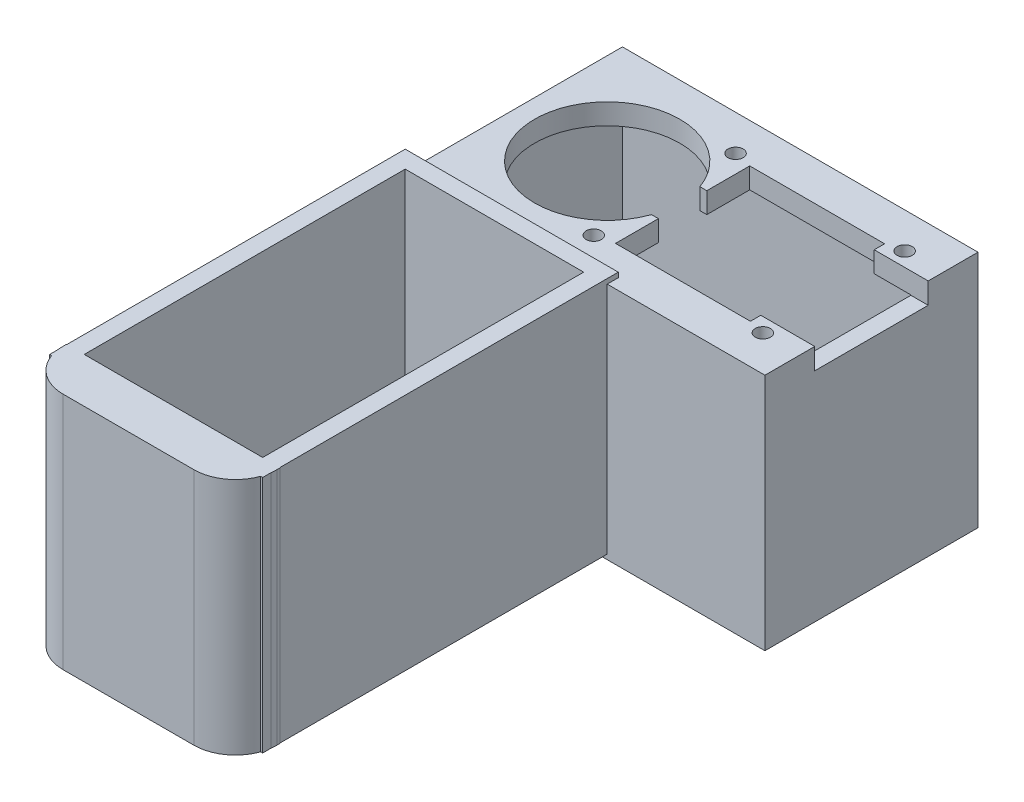
SolidWorks part; units mm, degrees
ref_plane "Front Plane" through (0, 0, 0) normal (0, 0, 1) x (1, 0, 0)
ref_plane "Top Plane" through (0, 0, 0) normal (0, 1, 0) x (1, 0, 0)
ref_plane "Right Plane" through (0, 0, 0) normal (1, 0, 0) x (0, 0, -1)
ref_plane "PZ_m38_200" through (0, 0, -38.2) normal (0, 0, 1) x (1, 0, 0)
sketch "S_box1" plane through (0, 0, -38.2) normal (0, 0, 1) x (1, 0, 0)
  line L0 (-15.4, -37.4) -> (15.4, -37.4)
  line L1 (15.4, -37.4) -> (15.4, -2.9)
  line L2 (15.4, -2.9) -> (-15.4, -2.9)
  line L3 (-15.4, -2.9) -> (-15.4, -37.4)
  dimension "P1" = 15.4
  dimension "P2" = 37.4
  dimension "P3" = 15.4
  dimension "P4" = 37.4
  dimension "P5" = 15.4
  dimension "P6" = 2.9
  dimension "P7" = 15.4
  dimension "P8" = 2.9
extrude "Boss_1" add sketch "S_box1" along normal blind 2.5
ref_plane "PZ_p10_700" through (0, 0, 10.7) normal (0, 0, 1) x (1, 0, 0)
sketch "S_box2" plane through (0, 0, 10.7) normal (0, 0, 1) x (1, 0, 0)
  line L0 (-15.4, -37.4) -> (15.4, -37.4)
  line L1 (15.4, -37.4) -> (15.4, -2.9)
  line L2 (15.4, -2.9) -> (-15.4, -2.9)
  line L3 (-15.4, -2.9) -> (-15.4, -37.4)
  dimension "P1" = 15.4
  dimension "P2" = 37.4
  dimension "P3" = 15.4
  dimension "P4" = 37.4
  dimension "P5" = 15.4
  dimension "P6" = 2.9
  dimension "P7" = 15.4
  dimension "P8" = 2.9
extrude "Boss_2" add sketch "S_box2" along normal blind 2.5
sketch "S_box3" plane through (0, 0, -38.2) normal (0, 0, 1) x (1, 0, 0)
  line L0 (-15.4, -37.4) -> (-12.9, -37.4)
  line L1 (-12.9, -37.4) -> (-12.9, -2.9)
  line L2 (-12.9, -2.9) -> (-15.4, -2.9)
  line L3 (-15.4, -2.9) -> (-15.4, -37.4)
  dimension "P1" = 15.4
  dimension "P2" = 37.4
  dimension "P3" = 12.9
  dimension "P4" = 37.4
  dimension "P5" = 12.9
  dimension "P6" = 2.9
  dimension "P7" = 15.4
  dimension "P8" = 2.9
extrude "Boss_3" add sketch "S_box3" along normal blind 51.4
sketch "S_box4" plane through (0, 0, -38.2) normal (0, 0, 1) x (1, 0, 0)
  line L0 (12.9, -37.4) -> (15.4, -37.4)
  line L1 (15.4, -37.4) -> (15.4, -2.9)
  line L2 (15.4, -2.9) -> (12.9, -2.9)
  line L3 (12.9, -2.9) -> (12.9, -37.4)
  dimension "P1" = 12.9
  dimension "P2" = 37.4
  dimension "P3" = 15.4
  dimension "P4" = 37.4
  dimension "P5" = 15.4
  dimension "P6" = 2.9
  dimension "P7" = 12.9
  dimension "P8" = 2.9
extrude "Boss_4" add sketch "S_box4" along normal blind 51.4
sketch "S_box5" plane through (0, 0, -38.2) normal (0, 0, 1) x (1, 0, 0)
  line L0 (-15.4, -37.4) -> (15.4, -37.4)
  line L1 (15.4, -37.4) -> (15.4, -34.4)
  line L2 (15.4, -34.4) -> (-15.4, -34.4)
  line L3 (-15.4, -34.4) -> (-15.4, -37.4)
  dimension "P1" = 15.4
  dimension "P2" = 37.4
  dimension "P3" = 15.4
  dimension "P4" = 37.4
  dimension "P5" = 15.4
  dimension "P6" = 34.4
  dimension "P7" = 15.4
  dimension "P8" = 34.4
extrude "Boss_5" add sketch "S_box5" along normal blind 51.4
ref_plane "PZ_m67_400" through (0, 0, -67.4) normal (0, 0, 1) x (1, 0, 0)
sketch "S_box6" plane through (0, 0, -67.4) normal (0, 0, 1) x (1, 0, 0)
  line L0 (-13.2, -38.1) -> (-10.7, -38.1)
  line L1 (-10.7, -38.1) -> (-10.7, -3.6)
  line L2 (-10.7, -3.6) -> (-13.2, -3.6)
  line L3 (-13.2, -3.6) -> (-13.2, -38.1)
  dimension "P1" = 13.2
  dimension "P2" = 38.1
  dimension "P3" = 10.7
  dimension "P4" = 38.1
  dimension "P5" = 10.7
  dimension "P6" = 3.6
  dimension "P7" = 13.2
  dimension "P8" = 3.6
extrude "Boss_6" add sketch "S_box6" along normal blind 30.8
sketch "S_box7" plane through (0, 0, -67.4) normal (0, 0, 1) x (1, 0, 0)
  line L0 (35.7, -38.1) -> (38.2, -38.1)
  line L1 (38.2, -38.1) -> (38.2, -3.6)
  line L2 (38.2, -3.6) -> (35.7, -3.6)
  line L3 (35.7, -3.6) -> (35.7, -38.1)
  dimension "P1" = 35.7
  dimension "P2" = 38.1
  dimension "P3" = 38.2
  dimension "P4" = 38.1
  dimension "P5" = 38.2
  dimension "P6" = 3.6
  dimension "P7" = 35.7
  dimension "P8" = 3.6
extrude "Boss_7" add sketch "S_box7" along normal blind 30.8
sketch "S_box8" plane through (0, 0, -67.4) normal (0, 0, 1) x (1, 0, 0)
  line L0 (-13.2, -38.1) -> (38.2, -38.1)
  line L1 (38.2, -38.1) -> (38.2, -3.6)
  line L2 (38.2, -3.6) -> (-13.2, -3.6)
  line L3 (-13.2, -3.6) -> (-13.2, -38.1)
  dimension "P1" = 13.2
  dimension "P2" = 38.1
  dimension "P3" = 38.2
  dimension "P4" = 38.1
  dimension "P5" = 38.2
  dimension "P6" = 3.6
  dimension "P7" = 13.2
  dimension "P8" = 3.6
extrude "Boss_8" add sketch "S_box8" along normal blind 2.5
ref_plane "PZ_m39_100" through (0, 0, -39.1) normal (0, 0, 1) x (1, 0, 0)
sketch "S_box9" plane through (0, 0, -39.1) normal (0, 0, 1) x (1, 0, 0)
  line L0 (-13.2, -38.1) -> (38.2, -38.1)
  line L1 (38.2, -38.1) -> (38.2, -3.6)
  line L2 (38.2, -3.6) -> (-13.2, -3.6)
  line L3 (-13.2, -3.6) -> (-13.2, -38.1)
  dimension "P1" = 13.2
  dimension "P2" = 38.1
  dimension "P3" = 38.2
  dimension "P4" = 38.1
  dimension "P5" = 38.2
  dimension "P6" = 3.6
  dimension "P7" = 13.2
  dimension "P8" = 3.6
extrude "Boss_9" add sketch "S_box9" along normal blind 2.5
sketch "S_box10" plane through (0, 0, -67.4) normal (0, 0, 1) x (1, 0, 0)
  line L0 (-13.2, -6.6) -> (38.2, -6.6)
  line L1 (38.2, -6.6) -> (38.2, -3.6)
  line L2 (38.2, -3.6) -> (-13.2, -3.6)
  line L3 (-13.2, -3.6) -> (-13.2, -6.6)
  dimension "P1" = 13.2
  dimension "P2" = 6.6
  dimension "P3" = 38.2
  dimension "P4" = 6.6
  dimension "P5" = 38.2
  dimension "P6" = 3.6
  dimension "P7" = 13.2
  dimension "P8" = 3.6
extrude "Boss_10" add sketch "S_box10" along normal blind 30.8
ref_plane "PY_m37_400" through (0, -37.4, 0) normal (0, 1, 0) x (1, 0, 0)
sketch "S_prism11" plane through (0, -37.4, 0) normal (0, 1, 0) x (1, 0, 0)
  line L0 (-15.45, -10.75) -> (15.45, -10.75)
  line L1 (15.45, -10.75) -> (15.45, -11.2)
  line L2 (9.45, -17.2) -> (-9.45, -17.2)
  line L3 (-15.45, -11.2) -> (-15.45, -10.75)
  arc A0 (15.45, -11.2) -> (9.45, -17.2) centre (9.4499, -11.1999) cw
  arc A1 (-9.45, -17.2) -> (-15.45, -11.2) centre (-9.4499, -11.1999) cw
extrude "Boss_11" add sketch "S_prism11" along normal blind 34.5
ref_plane "PY_m37_500" through (0, -37.5, 0) normal (0, 1, 0) x (1, 0, 0)
sketch "S_hole12" plane through (0, -37.5, 0) normal (0, 1, 0) x (1, 0, 0)
  circle A0 centre (0, 0) radius 10.5
  dimension "D1_S_hole12" = 21
extrude "Hole_12" cut sketch "S_hole12" along normal blind 3.2
ref_plane "PZ_m30_400" through (0, 0, -30.4) normal (0, 0, 1) x (1, 0, 0)
sketch "S_cut13" plane through (0, 0, -30.4) normal (0, 0, 1) x (1, 0, 0)
  line L0 (-9.7, -37.5) -> (9.7, -37.5)
  line L1 (9.7, -37.5) -> (9.7, -34.35)
  line L2 (9.7, -34.35) -> (-9.7, -34.35)
  line L3 (-9.7, -34.35) -> (-9.7, -37.5)
  dimension "P1" = 9.7
  dimension "P2" = 37.5
  dimension "P3" = 9.7
  dimension "P4" = 37.5
  dimension "P5" = 9.7
  dimension "P6" = 34.35
  dimension "P7" = 9.7
  dimension "P8" = 34.35
extrude "Pocket_13" cut sketch "S_cut13" along normal blind 19.5
ref_plane "PZ_m38_700" through (0, 0, -38.7) normal (0, 0, 1) x (1, 0, 0)
sketch "S_cut14" plane through (0, 0, -38.7) normal (0, 0, 1) x (1, 0, 0)
  line L0 (-8.2, -37.5) -> (8.2, -37.5)
  line L1 (8.2, -37.5) -> (8.2, -34.35)
  line L2 (8.2, -34.35) -> (-8.2, -34.35)
  line L3 (-8.2, -34.35) -> (-8.2, -37.5)
  dimension "P1" = 8.2
  dimension "P2" = 37.5
  dimension "P3" = 8.2
  dimension "P4" = 37.5
  dimension "P5" = 8.2
  dimension "P6" = 34.35
  dimension "P7" = 8.2
  dimension "P8" = 34.35
extrude "Pocket_14" cut sketch "S_cut14" along normal blind 8.3
ref_plane "PZ_m11_000" through (0, 0, -11) normal (0, 0, 1) x (1, 0, 0)
sketch "S_cut15" plane through (0, 0, -11) normal (0, 0, 1) x (1, 0, 0)
  line L0 (-3.5, -37.5) -> (3.5, -37.5)
  line L1 (3.5, -37.5) -> (3.5, -34.35)
  line L2 (3.5, -34.35) -> (-3.5, -34.35)
  line L3 (-3.5, -34.35) -> (-3.5, -37.5)
  dimension "P1" = 3.5
  dimension "P2" = 37.5
  dimension "P3" = 3.5
  dimension "P4" = 37.5
  dimension "P5" = 3.5
  dimension "P6" = 34.35
  dimension "P7" = 3.5
  dimension "P8" = 34.35
extrude "Pocket_15" cut sketch "S_cut15" along normal blind 11
sketch "S_hole16" plane through (0, -37.5, 0) normal (0, 1, 0) x (1, 0, 0)
  circle A0 centre (-10.25, 8.3) radius 1.1
  dimension "D1_S_hole16" = 2.2
  dimension "P2" = 10.25
  dimension "P3" = 8.3
extrude "Hole_16" cut sketch "S_hole16" along normal blind 3.2
sketch "S_hole17" plane through (0, -37.5, 0) normal (0, 1, 0) x (1, 0, 0)
  circle A0 centre (10.25, 8.3) radius 1.1
  dimension "D1_S_hole17" = 2.2
  dimension "P2" = 10.25
  dimension "P3" = 8.3
extrude "Hole_17" cut sketch "S_hole17" along normal blind 3.2
sketch "S_hole18" plane through (0, -37.5, 0) normal (0, 1, 0) x (1, 0, 0)
  circle A0 centre (-10.25, 32.75) radius 1.1
  dimension "D1_S_hole18" = 2.2
  dimension "P2" = 10.25
  dimension "P3" = 32.75
extrude "Hole_18" cut sketch "S_hole18" along normal blind 3.2
sketch "S_hole19" plane through (0, -37.5, 0) normal (0, 1, 0) x (1, 0, 0)
  circle A0 centre (10.25, 32.75) radius 1.1
  dimension "D1_S_hole19" = 2.2
  dimension "P2" = 10.25
  dimension "P3" = 32.75
extrude "Hole_19" cut sketch "S_hole19" along normal blind 3.2
ref_plane "PY_m6_700" through (0, -6.7, 0) normal (0, 1, 0) x (1, 0, 0)
sketch "S_hole20" plane through (0, -6.7, 0) normal (0, 1, 0) x (1, 0, 0)
  circle A0 centre (0, 52) radius 10.5
  dimension "D1_S_hole20" = 21
  dimension "P2" = 52
extrude "Hole_20" cut sketch "S_hole20" along normal blind 3.2
ref_plane "PZ_m61_700" through (0, 0, -61.7) normal (0, 0, 1) x (1, 0, 0)
sketch "S_cut21" plane through (0, 0, -61.7) normal (0, 0, 1) x (1, 0, 0)
  line L0 (10.9, -6.65) -> (30.4, -6.65)
  line L1 (30.4, -6.65) -> (30.4, -3.5)
  line L2 (30.4, -3.5) -> (10.9, -3.5)
  line L3 (10.9, -3.5) -> (10.9, -6.65)
  dimension "P1" = 10.9
  dimension "P2" = 6.65
  dimension "P3" = 30.4
  dimension "P4" = 6.65
  dimension "P5" = 30.4
  dimension "P6" = 3.5
  dimension "P7" = 10.9
  dimension "P8" = 3.5
extrude "Pocket_21" cut sketch "S_cut21" along normal blind 19.4
ref_plane "PZ_m60_200" through (0, 0, -60.2) normal (0, 0, 1) x (1, 0, 0)
sketch "S_cut22" plane through (0, 0, -60.2) normal (0, 0, 1) x (1, 0, 0)
  line L0 (30.4, -6.65) -> (38.7, -6.65)
  line L1 (38.7, -6.65) -> (38.7, -3.5)
  line L2 (38.7, -3.5) -> (30.4, -3.5)
  line L3 (30.4, -3.5) -> (30.4, -6.65)
  dimension "P1" = 30.4
  dimension "P2" = 6.65
  dimension "P3" = 38.7
  dimension "P4" = 6.65
  dimension "P5" = 38.7
  dimension "P6" = 3.5
  dimension "P7" = 30.4
  dimension "P8" = 3.5
extrude "Pocket_22" cut sketch "S_cut22" along normal blind 16.4
ref_plane "PZ_m55_500" through (0, 0, -55.5) normal (0, 0, 1) x (1, 0, 0)
sketch "S_cut23" plane through (0, 0, -55.5) normal (0, 0, 1) x (1, 0, 0)
  line L0 (0, -6.65) -> (11, -6.65)
  line L1 (11, -6.65) -> (11, -3.5)
  line L2 (11, -3.5) -> (0, -3.5)
  line L3 (0, -3.5) -> (0, -6.65)
  dimension "P1" = 6.65
  dimension "P2" = 11
  dimension "P3" = 6.65
  dimension "P4" = 11
  dimension "P5" = 3.5
  dimension "P6" = 3.5
extrude "Pocket_23" cut sketch "S_cut23" along normal blind 7
sketch "S_hole24" plane through (0, -6.7, 0) normal (0, 1, 0) x (1, 0, 0)
  circle A0 centre (8.3, 62.25) radius 1.1
  dimension "D1_S_hole24" = 2.2
  dimension "P2" = 8.3
  dimension "P3" = 62.25
extrude "Hole_24" cut sketch "S_hole24" along normal blind 3.2
sketch "S_hole25" plane through (0, -6.7, 0) normal (0, 1, 0) x (1, 0, 0)
  circle A0 centre (8.3, 41.75) radius 1.1
  dimension "D1_S_hole25" = 2.2
  dimension "P2" = 8.3
  dimension "P3" = 41.75
extrude "Hole_25" cut sketch "S_hole25" along normal blind 3.2
sketch "S_hole26" plane through (0, -6.7, 0) normal (0, 1, 0) x (1, 0, 0)
  circle A0 centre (32.75, 62.25) radius 1.1
  dimension "D1_S_hole26" = 2.2
  dimension "P2" = 32.75
  dimension "P3" = 62.25
extrude "Hole_26" cut sketch "S_hole26" along normal blind 3.2
sketch "S_hole27" plane through (0, -6.7, 0) normal (0, 1, 0) x (1, 0, 0)
  circle A0 centre (32.75, 41.75) radius 1.1
  dimension "D1_S_hole27" = 2.2
  dimension "P2" = 32.75
  dimension "P3" = 41.75
extrude "Hole_27" cut sketch "S_hole27" along normal blind 3.2
equation "\"plate_t\" = 3"
equation "\"clearance\" = 0.5"
